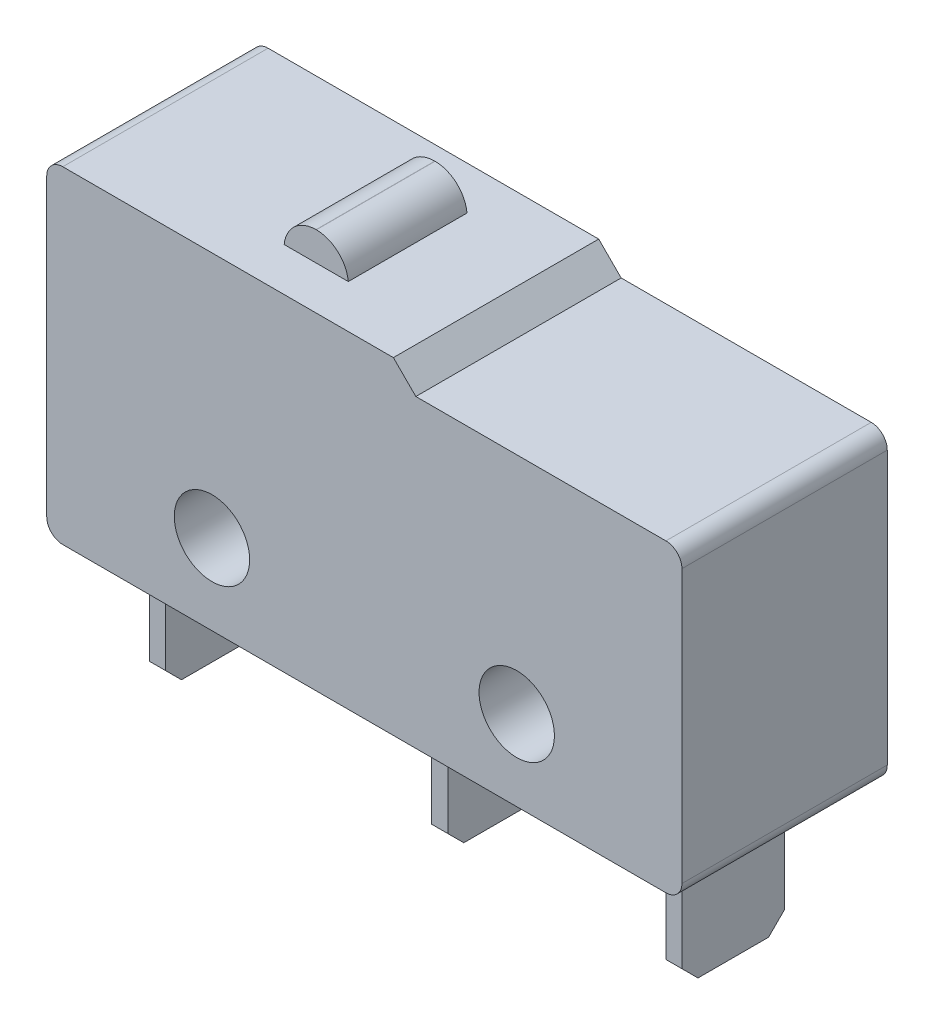
SolidWorks part; units mm, degrees
ref_plane "前视基准面" through (0, 0, 0) normal (0, 0, 1) x (1, 0, 0)
ref_plane "上视基准面" through (0, 0, 0) normal (0, 1, 0) x (1, 0, 0)
ref_plane "右视基准面" through (0, 0, 0) normal (1, 0, 0) x (0, 0, -1)
other "Configuration Table"
sketch "草图1" plane through (0, 0, 0) normal (0, 0, 1) x (1, 0, 0)
  line L1 (9.9, 5.1) -> (-9.9, 5.1)
  line L2 (9.9, 5.1) -> (9.9, -5.1)
  line L3 (9.9, -5.1) -> (-9.9, -5.1)
  line L4 (-9.9, 5.1) -> (-9.9, -5.1)
  line L5 (9.9, 5.1) -> (-9.9, -5.1) construction
  line L6 (9.9, -5.1) -> (-9.9, 5.1) construction
  point P0 (0, 0)
  dimension "D1" = 10.2
  dimension "D2" = 19.8
extrude "凸台-拉伸1" add sketch "草图1" along normal blind 6.4
sketch "草图2" plane through (0, 0, 6.4) normal (0, 0, 1) x (1, 0, 0)
  line L0 (0.0073, 5.998) -> (1.6053, 4.4)
  line L1 (1.6053, 4.4) -> (11.594, 4.4)
  line L2 (11.594, 4.4) -> (11.594, 6.8418)
  line L3 (11.594, 6.8418) -> (0.0073, 6.9858)
  line L4 (0.0073, 6.9858) -> (0.0073, 6.1215)
  line L5 (-9.9, -5.1) -> (9.9, -5.1) construction
  line L6 (9.9, 5.1) -> (-9.9, 5.1) construction
  dimension "D1" = 9.5
  dimension "D2" = 45
extrude "切除-拉伸1" cut sketch "草图2" against normal through all and the other way through all
sketch "草图3" plane through (0, 0, 6.4) normal (0, 0, 1) x (1, 0, 0)
  line L0 (0, 0) -> (0, -5.1) construction
  line L1 (-9.9, -5.1) -> (9.9, -5.1) construction
  line L2 (4.75, -2.6) -> (-4.75, -2.6) construction
  circle A0 centre (-4.75, -2.6) radius 1.175
  circle A1 centre (4.75, -2.6) radius 1.175
  point P12 (0, -2.6)
  dimension "D3" = 2.35
  dimension "D1" = 9.5
  dimension "D4" = 2.5
extrude "切除-拉伸2" cut sketch "草图3" against normal through all
sketch "草图4" plane through (0, 5.1, 0) normal (0, 1, 0) x (1, 0, 0)
  line L0 (-9.9, -3.2) -> (-2.85, -3.2) construction
  line L1 (-9.9, -6.4) -> (-9.9, 0) construction
  line L2 (3.575, -6.4) -> (5.925, -6.4) construction
  line L3 (3.575, -6.4) -> (5.925, -6.4)
  line L4 (4.75, -6.4) -> (4.75, -3.2) construction
  line L6 (-3.85, -1.35) -> (-1.85, -1.35)
  line L7 (-3.85, -1.35) -> (-3.85, -5.05)
  line L8 (-3.85, -5.05) -> (-1.85, -5.05)
  line L9 (-1.85, -1.35) -> (-1.85, -5.05)
  line L10 (-3.85, -1.35) -> (-1.85, -5.05) construction
  line L11 (-3.85, -5.05) -> (-1.85, -1.35) construction
  dimension "D2" = 2
  dimension "D1" = 7.6
  dimension "D3" = 3.7
extrude "凸台-拉伸2" add sketch "草图4" along normal offset from surface (0.9 mm away) 11.1 contours L9 L6 L7 L8 up to face at (0, -5.1, 3.2)
fillet "圆角2" radius 0.5 4 edges at (9.9, 4.4, 3.2) (9.9, -5.1, 3.2) (-9.9, -5.1, 3.2) (-9.9, 5.1, 3.2)
fillet "圆角3" radius 1 2 edges at (-1.85, 6, 3.2) (-3.85, 6, 3.2)
sketch "草图6" plane through (0, -5.1, 0) normal (0, -1, 0) x (1, 0, 0)
  line L0 (-9.9, 3.2) -> (9.9, 3.2) construction
  line L1 (-9.9, 0) -> (-9.9, 6.4) construction
  line L2 (9.9, 6.4) -> (9.9, 0) construction
  line L4 (-8.3, 4.8) -> (-7.8, 4.8)
  line L5 (-8.3, 4.8) -> (-8.3, 1.6)
  line L6 (-8.3, 1.6) -> (-7.8, 1.6)
  line L7 (-7.8, 4.8) -> (-7.8, 1.6)
  line L8 (-8.3, 4.8) -> (-7.8, 1.6) construction
  line L9 (-8.3, 1.6) -> (-7.8, 4.8) construction
  line L10 (0.5, 4.8) -> (1, 4.8)
  line L11 (0.5, 4.8) -> (0.5, 1.6)
  line L12 (0.5, 1.6) -> (1, 1.6)
  line L13 (1, 4.8) -> (1, 1.6)
  line L14 (0.5, 4.8) -> (1, 1.6) construction
  line L15 (0.5, 1.6) -> (1, 4.8) construction
  line L16 (7.8, 4.8) -> (8.3, 4.8)
  line L17 (7.8, 4.8) -> (7.8, 1.6)
  line L18 (7.8, 1.6) -> (8.3, 1.6)
  line L19 (8.3, 4.8) -> (8.3, 1.6)
  line L20 (7.8, 4.8) -> (8.3, 1.6) construction
  line L21 (7.8, 1.6) -> (8.3, 4.8) construction
  point P6 (-8.05, 3.2)
  point P11 (0.75, 3.2)
  point P16 (8.05, 3.2)
  dimension "D1" = 0.5
  dimension "D2" = 3.2
  dimension "D3" = 1.85
  dimension "D4" = 8.8
  dimension "D5" = 7.3
extrude "凸台-拉伸3" add sketch "草图6" along normal blind 3.9
chamfer "倒角1" distance 0.5 angle 45 6 edges at (8.05, -9, 1.6) (8.05, -9, 4.8) (0.75, -9, 4.8) (0.75, -9, 1.6) (-8.05, -9, 1.6) (-8.05, -9, 4.8)
